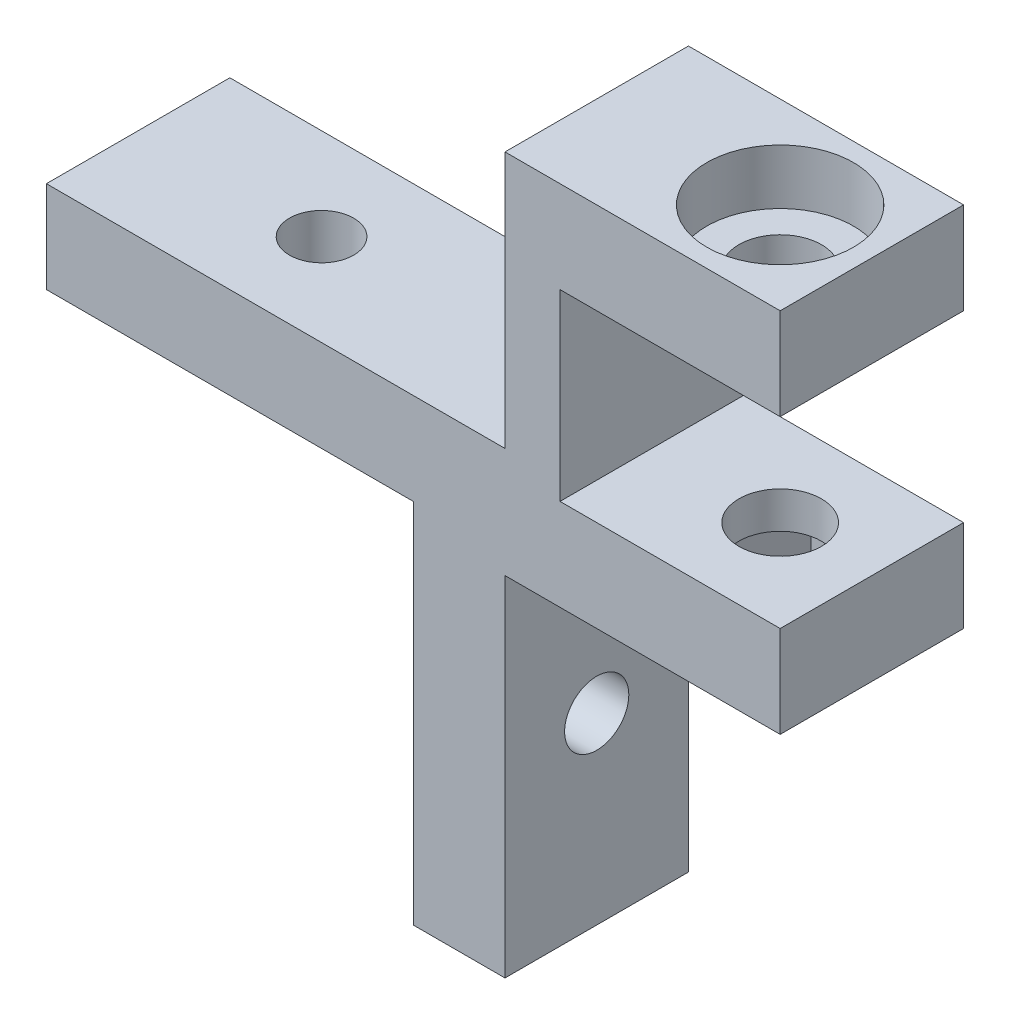
SolidWorks part; units mm, degrees
material "ABS"
ref_plane "Front Plane" through (0, 0, 0) normal (0, 0, 1) x (1, 0, 0)
ref_plane "Top Plane" through (0, 0, 0) normal (0, 1, 0) x (1, 0, 0)
ref_plane "Right Plane" through (0, 0, 0) normal (1, 0, 0) x (0, 0, -1)
sketch "Sketch2" plane through (0, 0, 0) normal (0, 0, 1) x (1, 0, 0)
  line L1 (-12.5, -12.5) -> (12.5, -12.5)
  line L2 (-12.5, -12.5) -> (-12.5, 12.5)
  line L3 (-12.5, 12.5) -> (12.5, 12.5)
  line L4 (12.5, -12.5) -> (12.5, 12.5)
  line L5 (-12.5, -12.5) -> (12.5, 12.5) construction
  line L6 (-12.5, 12.5) -> (12.5, -12.5) construction
  point P0 (0, 0)
  dimension "D1" = 25
  dimension "D2" = 25
extrude "Boss-Extrude1" add sketch "Sketch2" along normal blind 10
sketch "Sketch3" plane through (0, 0, 10) normal (0, 0, 1) x (1, 0, 0)
  line L1 (-12.5, -12.5) -> (7.5, -12.5)
  line L2 (-12.5, -12.5) -> (-12.5, 7.5)
  line L3 (-12.5, 7.5) -> (7.5, 7.5)
  line L4 (7.5, -12.5) -> (7.5, 7.5)
  dimension "D1" = 20
  dimension "D2" = 20
extrude "Cut-Extrude1" cut sketch "Sketch3" against normal through all
sketch "Sketch5" plane through (12.5, 0, 0) normal (1, 0, 0) x (0, 0, -1)
  line L0 (-10, -12.5) -> (-10, 12.5) construction
  line L1 (-10, 6.5) -> (0, 6.5)
  line L2 (-10, 6.5) -> (-10, 26.5)
  line L3 (-10, 26.5) -> (0, 26.5)
  line L4 (0, 6.5) -> (0, 26.5)
  line L5 (-10, 12.5) -> (0, 12.5) construction
  dimension "D1" = 14
  dimension "D2" = 6
extrude "Boss-Extrude2" add sketch "Sketch5" along normal blind 15
sketch "Sketch7" plane through (0, 0, 10) normal (0, 0, 1) x (1, 0, 0)
  line L0 (27.5, 26.5) -> (27.5, 6.5) construction
  line L1 (27.5, 21.5) -> (15.5, 21.5)
  line L2 (27.5, 21.5) -> (27.5, 11.5)
  line L3 (27.5, 11.5) -> (15.5, 11.5)
  line L4 (15.5, 21.5) -> (15.5, 11.5)
  line L5 (12.5, 12.5) -> (-12.5, 12.5) construction
  dimension "D1" = 10
  dimension "D2" = 1
  dimension "D3" = 12
extrude "Cut-Extrude2" cut sketch "Sketch7" against normal through all
sketch "Sketch8" plane through (0, 26.5, 0) normal (0, 1, 0) x (1, 0, 0)
  line L0 (12.5, -10) -> (12.5, 0) construction
  line L1 (27.5, 0) -> (12.5, 0) construction
  circle A0 centre (22.5, -5) radius 2.25
  dimension "D1" = 4.5
  dimension "D2" = 10
  dimension "D3" = 5
extrude "Cut-Extrude3" cut sketch "Sketch8" against normal through all
sketch "Sketch9" plane through (0, 12.5, 0) normal (0, 1, 0) x (1, 0, 0)
  line L0 (-12.5, -10) -> (-12.5, 0) construction
  line L2 (12.5, -10) -> (-12.5, -10) construction
  circle A0 centre (-2.5, -5) radius 1.75
  point P4 (0, 0)
  point P6 (-2.9188, -10)
  point P8 (0, 0)
  dimension "D1" = 3.5
  dimension "D2" = 10
  dimension "D3" = 5
extrude "Cut-Extrude4" cut sketch "Sketch9" against normal blind 15
sketch "Sketch10" plane through (12.5, 0, 0) normal (1, 0, 0) x (0, 0, -1)
  line L0 (-10, -12.5) -> (-10, 6.5) construction
  line L1 (-10, -12.5) -> (0, -12.5) construction
  circle A0 centre (-5, -2.5) radius 1.75
  dimension "D3" = 3.5
  dimension "D1" = 5
  dimension "D2" = 10
extrude "Cut-Extrude5" cut sketch "Sketch10" against normal blind 15
hole_wizard "CBORE for M4 Hex Socket Head Cap Screw1" positions "Sketch11" profile "Sketch12" counterbore size "M4" standard "ISO" end condition through all
sketch "Sketch11" plane through (0, 26.5, 0) normal (0, 1, 0) x (1, 0, 0)
  point P0 (22.5, -5)
sketch "Sketch12" plane through (22.5, 26.5, 5) normal (1, 0, 0) x (0, 0, 1)
  line L0 (0, 0) -> (0, 39)
  line L1 (0, 39) -> (2.25, 39)
  line L3 (2.25, 39) -> (2.25, 3)
  line L4 (2.25, 3) -> (4, 3)
  line L5 (4, 3) -> (4, 0)
  line L7 (4, 0) -> (0, 0)
  line L11 (0, -6.35) -> (0, 107.95) construction
  dimension "Thru Hole Dia." = 4.5
  dimension "Thru Hole Depth" = 39
  dimension "C'Bore Dia." = 8
  dimension "C'Bore Depth" = 3
sketch "Sketch13" plane through (0, 6.5, 0) normal (0, -1, 0) x (1, 0, 0)
  line L1 (17.8812, 5) -> (20.1906, 1)
  line L2 (20.1906, 1) -> (24.8094, 1)
  line L3 (24.8094, 1) -> (27.1188, 5)
  line L4 (27.1188, 5) -> (24.8094, 9)
  line L5 (24.8094, 9) -> (20.1906, 9)
  line L6 (20.1906, 9) -> (17.8812, 5)
  circle A0 centre (22.5, 5) radius 4 construction
  dimension "D1" = 8
extrude "Cut-Extrude6" cut sketch "Sketch13" against normal blind 3
